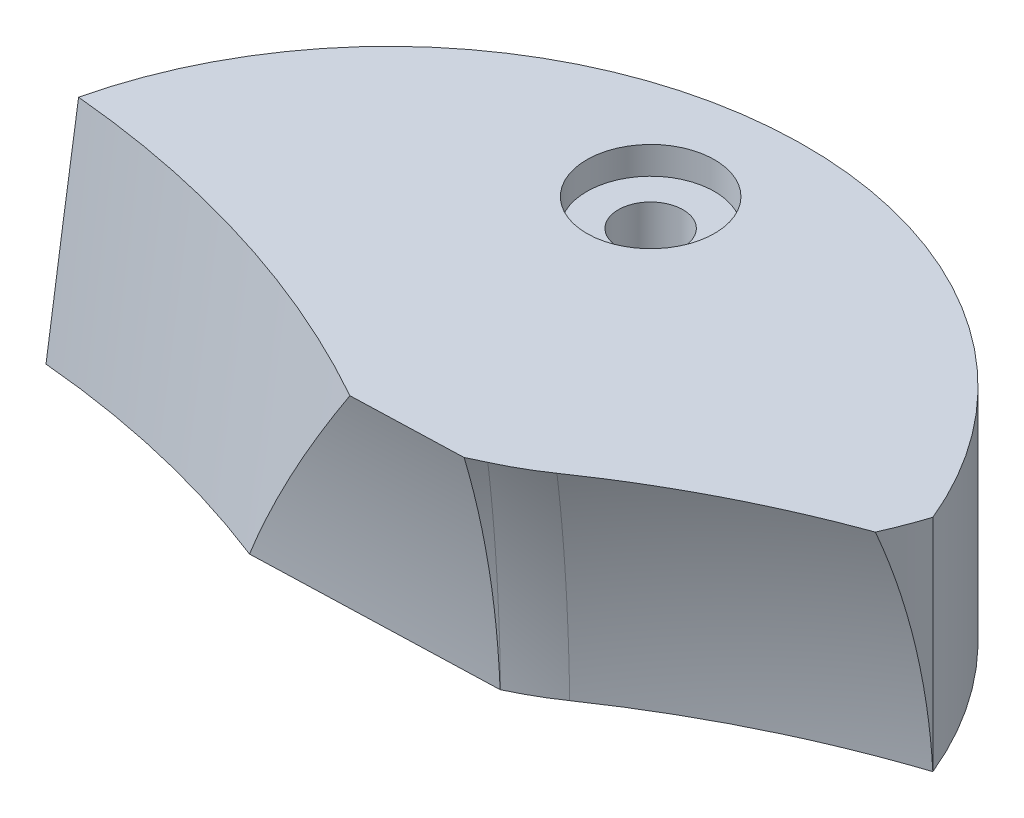
SolidWorks part; units mm, degrees
ref_plane "Front Plane" through (0, 0, 0) normal (0, 0, 1) x (1, 0, 0)
ref_plane "Top Plane" through (0, 0, 0) normal (0, 1, 0) x (1, 0, 0)
ref_plane "Right Plane" through (0, 0, 0) normal (1, 0, 0) x (0, 0, -1)
sketch "Sketch1" plane through (0, 0, 0) normal (0, 1, 0) x (1, 0, 0)
  circle A0 centre (0, 0) radius 16
  dimension "D1" = 32
extrude "Boss-Extrude1" add sketch "Sketch1" along normal blind 8 contours A0
sketch "Sketch2" plane through (0, 8, 0) normal (0, 1, 0) x (1, 0, 0)
  circle A0 centre (0, 0) radius 2.32
  dimension "D1" = 4.64
extrude "Cut-Extrude1" cut sketch "Sketch2" against normal blind 1
sketch "Sketch3" plane through (0, 7, 0) normal (0, 1, 0) x (1, 0, 0)
  circle A0 centre (0, 0) radius 1.175
  dimension "D1" = 2.35
extrude "Cut-Extrude2" cut sketch "Sketch3" against normal through all
sketch "Sketch5" plane through (0, 0, 0) normal (0, -1, 0) x (1, 0, 0)
  circle A0 centre (0, 0) radius 2.3
  dimension "D1" = 4.6
extrude "Cut-Extrude3" cut sketch "Sketch5" against normal blind 2
ref_point "Point1"
ref_plane "Plane1" through (0, -1.3, 0) normal (0, 1, 0) x (1, 0, 0)
sketch "Sketch7" plane through (0, -1.3, 0) normal (0, 1, 0) x (1, 0, 0)
  line L0 (26.088, -3.1982) -> (26.088, -72.9782)
  circle A2 centre (26.088, -38.0882) radius 34.89
  circle A3 centre (26.088, -38.0882) radius 34.89
  point P2 (19.4807, -7.9991)
  dimension "D1" = 0.6
revolve "Cut-Revolve1" cut sketch "Sketch7" angle 360 about L0 region at (11.2802, -1.3, 38.0882)
sketch "Sketch16" plane through (0, -1.3, 0) normal (0, 1, 0) x (1, 0, 0)
  line L0 (26.088, -38.0882) -> (0, 0) construction
  line L1 (6.372, -9.303) -> (16.6558, -4.4974) construction
  line L2 (6.372, -9.303) -> (15.7371, -2.8885) construction
  line L3 (0, 0) -> (19.5446, -41.8247) construction
  line L4 (19.5446, -41.8247) -> (26.088, -38.0882)
  line L5 (13.1999, -76.133) -> (25.8893, -7.5164)
  circle A1 centre (0, 0) radius 11.276
  circle A2 centre (26.088, -38.0882) radius 34.89
  circle A3 centre (26.088, -38.0882) radius 34.89
  arc A4 (14.6327, -6.4718) -> (0.7471, -15.9825) centre (0, 0) ccw construction
  circle A5 centre (19.5446, -41.8247) radius 34.89
  point P16 (0, 0)
  dimension "D2" = 22.5519
  dimension "D3" = 9.362
  dimension "D4" = 9.362
  dimension "D1" = 0.6
revolve "Cut-Revolve10" cut sketch "Sketch16" angle 360 about L5 region at (8.071, -1.3, 35.7845) region at (12.972, -1.3, 73.3745)
revolve "Cut-Revolve12" cut sketch "Sketch16<4>" angle 360 about L4 region at (5.5971, -1.3, 9.8017)
sketch "Sketch16<4>" plane through (0, -1.3, 0) normal (0, 1, 0) x (1, 0, 0) same geometry as "Sketch16"
sketch "Sketch17" plane through (0, -1.3, 0) normal (0, 1, 0) x (1, 0, 0)
  line L0 (-16.7976, -43.0016) -> (0, 0) construction
  line L1 (0, 0) -> (19.5446, -41.8247) construction
  circle A0 centre (-16.7976, -43.0016) radius 34.89
  arc A1 (5.4019, -11.3156) -> (-1.8628, -15.8912) centre (19.5446, -41.8247) ccw construction
  arc A2 (5.4019, -11.3156) -> (-1.8628, -15.8912) centre (19.5446, -41.8247) ccw
  circle A3 centre (19.5446, -41.8247) radius 34.89 construction
  point P5 (1.6229, -13.3706)
  point P10 (-16.7976, -43.0016)
  dimension "D1" = 46.384
extrude "Cut-Extrude6" cut sketch "Sketch17" along normal through all contours A0 region at (-16.7976, -1.3, 43.0016)
sketch "Sketch18" plane through (0, -1.3, 0) normal (0, 1, 0) x (1, 0, 0)
  line L0 (-4.1028, -10.5031) -> (4.7737, -10.2156)
  line L1 (0, 0) -> (19.5446, -41.8247) construction
  line L2 (-16.7976, -43.0016) -> (0, 0) construction
  line L3 (-16.7976, -43.0016) -> (19.5446, -41.8247)
  line L4 (19.5446, -41.8247) -> (4.7737, -10.2156)
  line L5 (-4.1028, -10.5031) -> (-16.7976, -43.0016)
  circle A2 centre (19.5446, -41.8247) radius 34.89 construction
  circle A3 centre (-16.7976, -43.0016) radius 34.89 construction
revolve "Cut-Revolve13" cut sketch "Sketch18" angle 360 about L3
sketch "Sketch19" plane through (0, 8, 0) normal (0, 1, 0) x (1, 0, 0)
  line L0 (-0.2619, 2.3052) -> (-0.4891, 4.3052)
  line L1 (0, 0) -> (-0.2619, 2.3052) construction
  line L2 (0, 0) -> (1.2194, -10.7327) construction
  arc A0 (15.211, -4.9625) -> (-13.7099, -8.2485) centre (0, 0) ccw construction
  arc A1 (15.211, -4.9625) -> (-13.7099, -8.2485) centre (0, 0) ccw
  arc A2 (-13.7099, -8.2485) -> (15.211, -4.9625) centre (1.2194, -10.7327) cw
  circle A3 centre (0, 0) radius 2.32 construction
  arc M7 (14.6327, -6.4718) -> (-13.7099, -8.2485) centre (0, 0) ccw
  dimension "D1" = 2
extrude "Cut-Extrude7" cut sketch "Sketch19" against normal through all contours A2 M7 region at (-0.7707, 8, -6.7829)
chamfer "Chamfer1" distance 1 distance2 8 1 edges at (-7.2928, 8, 9.4312) first distance on face at (0, 8, 2.32)
